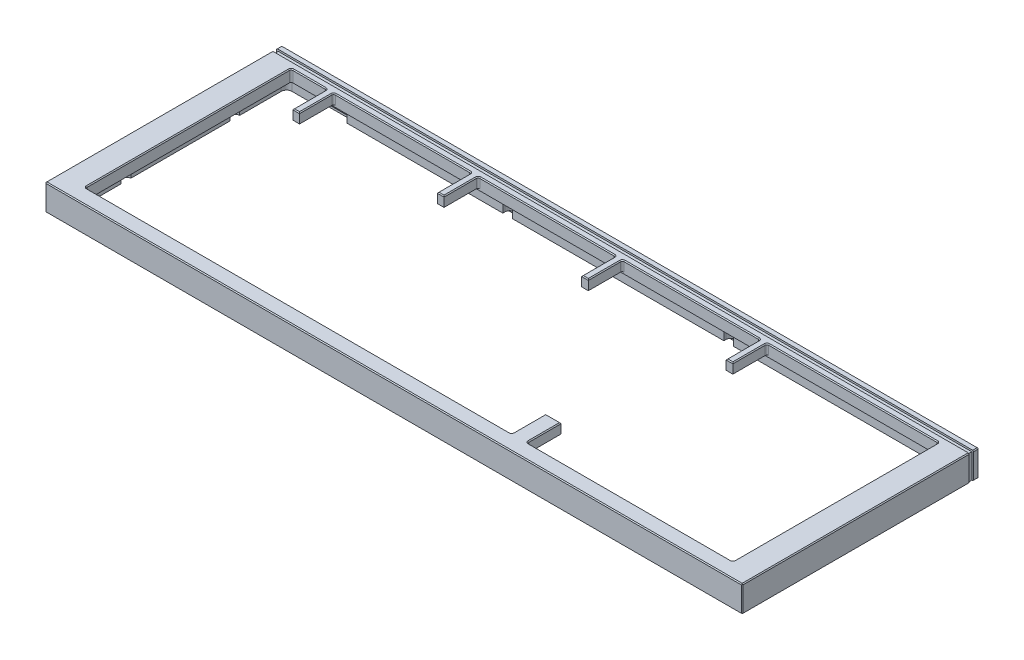
SolidWorks part; units mm, degrees
material "6061-T6 (SS)"
ref_plane "Front Plane" through (0, 0, 0) normal (0, 0, 1) x (1, 0, 0)
ref_plane "Top Plane" through (0, 0, 0) normal (0, 1, 0) x (1, 0, 0)
ref_plane "Right Plane" through (0, 0, 0) normal (1, 0, 0) x (0, 0, -1)
sketch "Sketch1" plane through (0, 0, 0) normal (0, 1, 0) x (1, 0, 0)
  line L1 (0, 0) -> (390.74, 0)
  line L2 (0, 0) -> (0, 132.7)
  line L3 (0, 132.7) -> (390.74, 132.7)
  line L4 (390.74, 0) -> (390.74, 132.7)
  line L5 (13.92, 124) -> (376.82, 124)
  line L6 (13.92, 124) -> (13.92, 8.7)
  line L7 (13.92, 8.7) -> (376.82, 8.7)
  line L8 (376.82, 124) -> (376.82, 8.7)
  point P9 (195.37, 124)
  point P10 (195.37, 132.7)
  point P11 (13.92, 66.35)
  point P12 (0, 66.35)
  dimension "D1" = 362.9
  dimension "D2" = 115.3
  dimension "D3" = 8.7
  dimension "D4" = 13.92
extrude "Main Body" add sketch "Sketch1" along normal blind 14.8
sketch "Sketch2" plane through (0, 0, 0) normal (0, -1, 0) x (1, 0, 0)
  line L0 (390.74, -132.7) -> (0, -132.7) construction
  line L1 (388.74, -130.7) -> (2, -130.7)
  line L2 (388.74, -130.7) -> (388.74, -2)
  line L3 (388.74, -2) -> (2, -2)
  line L4 (2, -130.7) -> (2, -2)
  line L5 (390.74, 0) -> (390.74, -132.7) construction
  point P4 (195.37, -130.7)
  point P7 (195.37, -132.7)
  point P8 (388.74, -66.35)
  point P11 (390.74, -66.35)
  dimension "D1" = 2
  dimension "D2" = 2
extrude "Alignment Guide" cut sketch "Sketch2" against normal blind 2 contours L2 L1 L4 L3
sketch "Sketch3" plane through (0, 14.8, 0) normal (0, 1, 0) x (1, 0, 0)
  line L0 (13.92, 8.7) -> (376.82, 8.7) construction
  line L1 (252.82, 27.8) -> (261.52, 27.8)
  line L2 (252.82, 27.8) -> (252.82, 8.7)
  line L3 (252.82, 8.7) -> (261.52, 8.7)
  line L4 (261.52, 27.8) -> (261.52, 8.7)
  line L5 (376.82, 8.7) -> (376.82, 124) construction
  line L6 (376.82, 124) -> (13.92, 124) construction
  line L7 (33.92, 124) -> (37.72, 124)
  line L8 (33.92, 124) -> (33.92, 104.9)
  line L9 (33.92, 104.9) -> (37.72, 104.9)
  line L10 (37.72, 124) -> (37.72, 104.9)
  line L11 (13.92, 124) -> (13.92, 8.7) construction
  line L12 (114.92, 124) -> (118.72, 124)
  line L13 (114.92, 124) -> (114.92, 104.9)
  line L14 (114.92, 104.9) -> (118.72, 104.9)
  line L15 (118.72, 124) -> (118.72, 104.9)
  line L16 (195.82, 124) -> (199.62, 124)
  line L17 (195.82, 124) -> (195.82, 104.9)
  line L18 (195.82, 104.9) -> (199.62, 104.9)
  line L19 (199.62, 124) -> (199.62, 104.9)
  line L20 (276.82, 124) -> (280.62, 124)
  line L21 (276.82, 124) -> (276.82, 104.9)
  line L22 (276.82, 104.9) -> (280.62, 104.9)
  line L23 (280.62, 124) -> (280.62, 104.9)
  point P8 (257.17, 8.7)
  dimension "D1" = 115.3
  dimension "D2" = 124
  dimension "D3" = 19.1
  dimension "D4" = 3.8
  dimension "D5" = 19.1
  dimension "D6" = 77.2
  dimension "D7" = 77.1
  dimension "D8" = 77.2
  dimension "D9" = 20
extrude "Blockers" add sketch "Sketch3" against normal blind 5.5
fillet "Fillet5" radius 1 14 edges at (280.62, 12.05, -124) (276.82, 12.05, -124) (195.82, 12.05, -124) (199.62, 12.05, -124) (118.72, 12.05, -124) (114.92, 12.05, -124) (33.92, 12.05, -124) (37.72, 12.05, -124) (13.92, 8.4, -124) (13.92, 8.4, -8.7) (252.82, 12.05, -8.7) (261.52, 12.05, -8.7) (376.82, 8.4, -8.7) (376.82, 8.4, -124)
sketch "Sketch4" plane through (0, 2, 0) normal (0, -1, 0) x (1, 0, 0)
  line L0 (0, 0) -> (390.74, 0) construction
  line L1 (381.27, -125.9) -> (9.47, -125.9)
  line L2 (381.27, -125.9) -> (381.27, -6.8)
  line L3 (381.27, -6.8) -> (9.47, -6.8)
  line L4 (9.47, -125.9) -> (9.47, -6.8)
  line L5 (390.74, 0) -> (390.74, -132.7) construction
  point P4 (195.37, -6.8)
  point P7 (195.37, 0)
  point P8 (381.27, -66.35)
  point P11 (390.74, -66.35)
  dimension "D1" = 119.1
  dimension "D2" = 371.8
extrude "PCB Cutout" cut sketch "Sketch4" against normal offset from surface (6.3 mm away) 6.5 up to face at (195.37, 14.8, -66.35)
fillet "Fillet4" radius 3 8 edges at (9.47, 5.15, -6.8) (9.47, 5.15, -125.9) (381.27, 5.15, -125.9) (381.27, 5.15, -6.8) (2, 1, -130.7) (2, 1, -2) (388.74, 1, -2) (388.74, 1, -130.7)
sketch "Sketch6" plane through (0, 2, 0) normal (0, -1, 0) x (1, 0, 0)
  line L0 (381.27, -9.8) -> (381.27, -122.9) construction
  line L1 (254.59, -127.1) -> (260.09, -127.1)
  line L2 (254.59, -127.1) -> (254.59, -125.9)
  line L3 (254.59, -125.9) -> (260.09, -125.9)
  line L4 (260.09, -127.1) -> (260.09, -125.9)
  line L5 (12.47, -125.9) -> (378.27, -125.9) construction
  line L11 (378.27, -6.8) -> (12.47, -6.8) construction
  line L16 (260.09, -6.8) -> (254.59, -6.8)
  line L17 (260.09, -6.8) -> (260.09, -4.8)
  line L18 (260.09, -4.8) -> (254.59, -4.8)
  line L19 (254.59, -6.8) -> (254.59, -4.8)
  line L21 (0, 0) -> (390.74, 0) construction
  line L24 (390.74, -66.35) -> (195.37, -66.35) construction
  line L25 (390.74, 0) -> (390.74, -132.7) construction
  line L26 (328.6755, -66.35) -> (328.6755, -130.7) construction
  line L27 (385.74, -130.7) -> (5, -130.7) construction
  line L28 (328.6755, -66.35) -> (328.6755, -8.7) construction
  line L29 (375.82, -8.7) -> (14.92, -8.7) construction
  line L55 (390.74, -132.7) -> (0, -132.7) construction
  line L56 (195.37, -132.7) -> (195.37, 0) construction
  line L57 (136.15, -6.8) -> (136.15, -4.8)
  line L58 (130.65, -4.8) -> (136.15, -4.8)
  line L59 (130.65, -6.8) -> (130.65, -4.8)
  line L60 (130.65, -6.8) -> (136.15, -6.8)
  line L61 (130.65, -127.1) -> (130.65, -125.9)
  line L62 (136.15, -125.9) -> (130.65, -125.9)
  line L63 (136.15, -127.1) -> (136.15, -125.9)
  line L64 (136.15, -127.1) -> (130.65, -127.1)
  circle A0 centre (381.07, -96.85) radius 2.75
  circle A1 centre (381.07, -35.85) radius 2.75
  circle A2 centre (257.34, -4.8) radius 2.75
  circle A3 centre (257.34, -127.1) radius 2.75
  circle A8 centre (133.4, -4.8) radius 2.75
  circle A9 centre (9.67, -35.85) radius 2.75
  circle A10 centre (9.67, -96.85) radius 2.75
  circle A11 centre (133.4, -127.1) radius 2.75
  point P25 (195.37, -66.35)
  point P32 (257.34, -125.9)
  point P33 (257.34, -6.8)
  line M17 (12.47, -6.8) -> (378.27, -6.8)
  line M18 (381.27, -9.8) -> (381.27, -122.9)
  line M19 (378.27, -125.9) -> (12.47, -125.9)
  line M20 (9.47, -122.9) -> (9.47, -9.8)
  dimension "D4" = 5.5
  dimension "D5" = 133.4
  dimension "D1" = 30.5
  dimension "D2" = 4.8
  dimension "D3" = 30.5
  dimension "D6" = 0.2
  dimension "D7" = 5.6
extrude "PlateTabs" cut sketch "Sketch6" against normal up to surface (6.3 mm away) contours A0 M18 | A1 M18 | A2 L19 M17 | L16 A2 L18 | A2 L17 M17 | L18 A2 | L1 A3 | L1 A3 L3 | A3 L2 M19 | A11 L64 | A11 L64 L62 | A10 M20 | A9 M20 | A8 L58 | A8 L60 L58 | A3 L4 M19 | A8 L59 M17 | L57 A8 M17 | A11 L63 M19 | L61 A11 M19 | A11 | L59 L58 L57 L60 | A3 region at (257.34, 2, -126.5102) region at (136.0681, 2, -126.1969) region at (257.34, 2, -128.2671) region at (254.6719, 2, -126.1969) region at (260.0081, 2, -126.1969) region at (133.4, 2, -126.5102) region at (133.4, 2, -128.2671) region at (130.7319, 2, -126.1969) region at (135.9001, 2, -6.317) region at (259.8401, 2, -6.317) region at (257.34, 2, -5.7445) region at (257.34, 2, -3.6329) region at (254.8399, 2, -6.317) region at (133.4, 2, -5.7445) region at (133.4, 2, -3.6329) region at (130.8999, 2, -6.317) region at (382.3459, 2, -96.85) region at (382.3459, 2, -35.85) region at (8.3941, 2, -96.85) region at (8.3941, 2, -35.85) up to face at (195.37, 8.3, -66.35)
sketch "Sketch9" plane through (0, 0, -132.7) normal (0, 0, -1) x (-1, 0, 0)
  line L1 (-40.9, 3) -> (-30.9, 3)
  line L2 (-40.9, 3) -> (-40.9, 6.8)
  line L3 (-40.9, 6.8) -> (-30.9, 6.8)
  line L4 (-30.9, 3) -> (-30.9, 6.8)
  line L7 (0, 14.8) -> (0, 0) construction
  line L8 (-390.74, 0) -> (0, 0) construction
  point P4 (-30.9, 4.9)
  point P6 (-35.9, 6.8)
  dimension "D1" = 4.9
  dimension "D2" = 3.8
  dimension "D3" = 10
  dimension "D4" = 35.9
extrude "USB Cutout" cut sketch "Sketch9" against normal up to surface (8.7 mm away) up to face at (164.89, 11.95, -124)
sketch "Sketch10" plane through (0, 0, -132.7) normal (0, 0, -1) x (-1, 0, 0)
  line L0 (-30.9, 6.8) -> (-40.9, 6.8) construction
  line L1 (-42.9, 8.8) -> (-28.9, 8.8)
  line L2 (-42.9, 8.8) -> (-42.9, 1)
  line L3 (-42.9, 1) -> (-28.9, 1)
  line L4 (-28.9, 8.8) -> (-28.9, 1)
  line L5 (-40.9, 6.8) -> (-40.9, 3) construction
  point P4 (-35.9, 8.8)
  point P7 (-35.9, 6.8)
  point P10 (-40.9, 4.9)
  point P11 (-42.9, 4.9)
  dimension "D1" = 2
  dimension "D2" = 2
extrude "USB Outline" cut sketch "Sketch10" against normal blind 1
sketch "Sketch11" plane through (0, 0, -125.9) normal (0, 0, 1) x (1, 0, 0)
  line L1 (43.4, 2) -> (28.4, 2)
  line L2 (43.4, 2) -> (43.4, 6.8)
  line L3 (43.4, 6.8) -> (28.4, 6.8)
  line L4 (28.4, 2) -> (28.4, 6.8)
  line L5 (30.9, 6.8) -> (40.9, 6.8) construction
  line L6 (40.9, 3) -> (30.9, 3) construction
  line L7 (12.47, 2) -> (130.65, 2) construction
  point P8 (35.9, 2)
  point P11 (35.9, 3)
  dimension "D1" = 15
extrude "PCB Clearance" cut sketch "Sketch11" against normal blind 3.9
fillet "Fillet6" radius 1.5 8 edges at (40.9, 6.8, -130.75) (30.9, 6.8, -130.75) (40.9, 3, -130.75) (42.9, 1, -132.2) (42.9, 8.8, -132.2) (28.9, 8.8, -132.2) (30.9, 3, -130.75) (28.9, 1, -132.2)
fillet "Fillet7" radius 2.5 2 edges at (28.4, 4.4, -129.8) (43.4, 4.4, -129.8)
sketch "Sketch12" plane through (0, 8.3, 0) normal (0, -1, 0) x (1, 0, 0)
  line L0 (195.37, -132.7) -> (195.37, 0) construction
  line L1 (390.74, -132.7) -> (0, -132.7) construction
  line L2 (14.92, -124) -> (375.82, -124) construction
  line L3 (0, 0) -> (390.74, 0) construction
  line L4 (390.74, 0) -> (390.74, -132.7) construction
  line L8 (376.82, -123) -> (376.82, -9.7) construction
  line L9 (375.82, -8.7) -> (14.92, -8.7) construction
  arc A0 (381.27, -38.5927) -> (381.27, -33.1073) centre (381.07, -35.85) ccw construction
  arc A1 (381.27, -99.5927) -> (381.27, -94.1073) centre (381.07, -96.85) ccw construction
  point P0 (257.34, -127.1)
  point P1 (381.42, -96.85)
  point P2 (381.42, -35.85)
  point P3 (257.34, -4.8)
  point P8 (133.4, -4.8)
  point P10 (9.32, -35.85)
  point P14 (9.32, -96.85)
  point P16 (133.4, -127.1)
  point P34 (383.82, -35.85)
  point P39 (383.82, -96.85)
  dimension "D1" = 3.1
  dimension "D2" = 3.9
  dimension "D3" = 4.6
  dimension "D4" = 133.4
sketch "Sketch14" plane through (0, 2, 0) normal (0, -1, 0) x (1, 0, 0)
  line L0 (195.37, -132.7) -> (195.37, 0) construction
  line L1 (390.74, -132.7) -> (0, -132.7) construction
  line L2 (0, 0) -> (390.74, 0) construction
  line L5 (195.37, -66.35) -> (390.74, -66.35) construction
  line L6 (390.74, 0) -> (390.74, -132.7) construction
  line L7 (388.74, -127.7) -> (388.74, -5) construction
  line L8 (385.74, -130.7) -> (5, -130.7) construction
  line L9 (385.74, -2) -> (5, -2) construction
  point P8 (385.04, -111.35)
  point P9 (385.04, -66.35)
  point P10 (385.04, -21.35)
  point P11 (280.74, -4.4)
  point P20 (280.74, -128.3)
  point P22 (110, -4.4)
  point P28 (110, -128.3)
  point P29 (5.7, -21.35)
  point P30 (5.7, -66.35)
  point P31 (5.7, -111.35)
  dimension "D1" = 2.4
  dimension "D2" = 2.4
  dimension "D3" = 110
  dimension "D4" = 45
  dimension "D5" = 45
  dimension "D6" = 3.7
chamfer "Chamfer1" distance 0.5 42 edges at (14.2129, 14.8, -8.9929) (133.37, 14.8, -8.7) (252.5271, 14.8, -8.9929) (252.82, 14.8, -18.75) (257.17, 14.8, -27.8) (261.52, 14.8, -18.75) (261.8129, 14.8, -8.9929) (319.17, 14.8, -8.7) (376.5271, 14.8, -8.9929) (376.82, 14.8, -66.35) (376.5271, 14.8, -123.7071) (328.72, 14.8, -124) (280.9129, 14.8, -123.7071) (280.62, 14.8, -113.95) (278.72, 14.8, -104.9) (276.82, 14.8, -113.95) (276.5271, 14.8, -123.7071) (238.22, 14.8, -124) (199.9129, 14.8, -123.7071) (199.62, 14.8, -113.95) (197.72, 14.8, -104.9) (195.82, 14.8, -113.95) (195.5271, 14.8, -123.7071) (157.27, 14.8, -124) (119.0129, 14.8, -123.7071) (118.72, 14.8, -113.95) (116.82, 14.8, -104.9) (114.92, 14.8, -113.95) (114.6271, 14.8, -123.7071) (76.32, 14.8, -124) (38.0129, 14.8, -123.7071) (37.72, 14.8, -113.95) (35.82, 14.8, -104.9) (33.92, 14.8, -113.95) (33.6271, 14.8, -123.7071) (23.92, 14.8, -124) (14.2129, 14.8, -123.7071) (13.92, 14.8, -66.35) (195.37, 14.8, -132.7) (390.74, 14.8, -66.35) (195.37, 14.8, 0) (0, 14.8, -66.35)
chamfer "Chamfer2" distance 0.5 8 edges at (0, 7.15, -132.7) (195.37, 0, -132.7) (390.74, 7.15, -132.7) (390.74, 0, -66.35) (390.74, 7.15, 0) (0, 7.15, 0) (195.37, 0, 0) (0, 0, -66.35)
sketch "Sketch27" plane through (0, 14.8, 0) normal (0, 1, 0) x (1, 0, 0)
  line L0 (0, 0.5) -> (0, 132.2) construction
  line L1 (0, 129.7) -> (390.74, 129.7)
  line L2 (0, 129.7) -> (0, 127.2)
  line L3 (0, 127.2) -> (390.74, 127.2)
  line L4 (390.74, 129.7) -> (390.74, 127.2)
  line L5 (390.74, 132.2) -> (390.74, 0.5) construction
  line L8 (0.5, 132.7) -> (390.24, 132.7) construction
  dimension "D1" = 2.5
  dimension "D2" = 3
extrude "Cut-Extrude11" cut sketch "Sketch27" against normal blind 1
sketch "Sketch28" plane through (0, 13.8, 0) normal (0, 1, 0) x (1, 0, 0)
  line L1 (0, 129.7) -> (1, 129.7)
  line L2 (0, 129.7) -> (0, 127.2)
  line L3 (0, 127.2) -> (1, 127.2)
  line L4 (1, 129.7) -> (1, 127.2)
  line L5 (389.74, 129.7) -> (390.74, 129.7)
  line L6 (389.74, 129.7) -> (389.74, 127.2)
  line L7 (389.74, 127.2) -> (390.74, 127.2)
  line L8 (390.74, 129.7) -> (390.74, 127.2)
  line L9 (390.74, 129.7) -> (0, 129.7) construction
  line L10 (0, 127.2) -> (390.74, 127.2) construction
  dimension "D1" = 1
  dimension "D2" = 1
extrude "Cut-Extrude12" cut sketch "Sketch28" against normal through all
sketch "Sketch21" [suppressed] plane through (0, 14.8, 0) normal (0, 1, 0) x (1, 0, 0)
  line L0 (0.5, 132.7) -> (390.24, 132.7) construction
  line L1 (382.53, 132.7) -> (385.03, 132.7)
  line L2 (382.53, 132.7) -> (382.53, 72.7)
  line L3 (382.53, 72.7) -> (385.03, 72.7)
  line L4 (385.03, 132.7) -> (385.03, 72.7)
  line L5 (390.74, 132.2) -> (390.74, 129.7) construction
  line L6 (390.74, 129.1) -> (294.74, 129.1)
  line L7 (390.74, 129.1) -> (390.74, 127.6)
  line L8 (390.74, 127.6) -> (294.74, 127.6)
  line L9 (294.74, 129.1) -> (294.74, 127.6)
  line L10 (362.9081, 132.2) -> (362.9081, 124.5) construction
  line L11 (390.24, 132.2) -> (0.5, 132.2) construction
  line L12 (281.62, 124.5) -> (375.82, 124.5) construction
  line L13 (365.5702, 129.1) -> (365.5702, 127.6) construction
  line L14 (377.32, 119.5259) -> (390.24, 119.5259) construction
  line L15 (377.32, 123) -> (377.32, 9.7) construction
  line L16 (390.24, 0.5) -> (390.24, 127.2) construction
  line L17 (382.53, 116.0504) -> (385.03, 116.0504) construction
  point P28 (383.78, 116.0504)
  point P29 (383.78, 119.5259)
  point P30 (365.5702, 128.35)
  point P31 (362.9081, 128.35)
  dimension "D1" = 2.5
  dimension "D2" = 1.5
  dimension "D3" = 60
  dimension "D4" = 96
extrude "Cut-Extrude5" [suppressed] cut sketch "Sketch21" against normal blind 1 contours L4 L3 L2 L1 | L8 L9 L6 L7
sketch "Sketch23" [suppressed] plane through (390.74, 0, 0) normal (1, 0, 0) x (0, 0, -1)
  line L0 (129.1, 13.8) -> (129.1, 14.3) construction
  line L1 (127.6, 13.8) -> (129.1, 13.8)
  line L2 (127.6, 13.8) -> (127.6, 0)
  line L3 (127.6, 0) -> (129.1, 0)
  line L4 (129.1, 13.8) -> (129.1, 0)
extrude "Cut-Extrude6" [suppressed] cut sketch "Sketch23" against normal blind 1
sketch "Sketch20" plane through (0, 14.8, 0) normal (0, 1, 0) x (1, 0, 0)
  line L0 (0, 0.5) -> (0, 127.2) construction
  line L1 (0, 129.1) -> (390.74, 129.1)
  line L2 (0, 129.1) -> (0, 127.6)
  line L3 (0, 127.6) -> (390.74, 127.6)
  line L4 (390.74, 129.1) -> (390.74, 127.6)
  line L5 (390.74, 132.2) -> (390.74, 129.7) construction
  line L6 (0.5, 132.7) -> (390.24, 132.7) construction
  line L7 (381.7523, 132.7) -> (384.2523, 132.7)
  line L8 (381.7523, 132.7) -> (381.7523, 0)
  line L9 (381.7523, 0) -> (384.2523, 0)
  line L10 (384.2523, 132.7) -> (384.2523, 0)
  line L11 (390.24, 0) -> (0.5, 0) construction
  line L12 (376.82, 111.1489) -> (390.74, 111.1489) construction
  line L13 (376.82, 9.7) -> (376.82, 123) construction
  line L14 (381.7523, 114.604) -> (384.2523, 114.604) construction
  line L15 (369.2566, 124.5) -> (369.2566, 132.2) construction
  line L16 (281.62, 124.5) -> (375.82, 124.5) construction
  line L17 (390.24, 132.2) -> (0.5, 132.2) construction
  line L18 (371.0168, 127.6) -> (371.0168, 129.1) construction
  point P30 (371.0168, 128.35)
  point P31 (369.2566, 128.35)
  dimension "D1" = 2.5
  dimension "D2" = 1.5
extrude "Cut-Extrude4" [suppressed] cut sketch "Sketch20" against normal blind 1
sketch "Sketch19" plane through (0, 14.8, 0) normal (0, 1, 0) x (1, 0, 0)
  line L0 (0.5, 132.7) -> (390.24, 132.7) construction
  line L1 (5.46, 132.7) -> (8.46, 132.7)
  line L2 (5.46, 132.7) -> (5.46, 0)
  line L3 (5.46, 0) -> (8.46, 0)
  line L4 (8.46, 132.7) -> (8.46, 0)
  line L7 (382.28, 132.7) -> (385.28, 132.7)
  line L8 (382.28, 132.7) -> (382.28, 0)
  line L9 (382.28, 0) -> (385.28, 0)
  line L10 (385.28, 132.7) -> (385.28, 0)
  line L11 (390.24, 0) -> (0.5, 0) construction
  line L12 (377.32, 110.209) -> (390.24, 110.209) construction
  line L13 (377.32, 123) -> (377.32, 9.7) construction
  line L14 (390.24, 0.5) -> (390.24, 127.2) construction
  line L15 (382.28, 106.8719) -> (385.28, 106.8719) construction
  line L16 (0.5, 106.8719) -> (13.42, 106.8719) construction
  line L17 (0.5, 132.2) -> (0.5, 129.7) construction
  line L18 (13.42, 9.7) -> (13.42, 123) construction
  line L19 (5.46, 102.7297) -> (8.46, 102.7297) construction
  point P12 (383.78, 106.8719)
  point P14 (383.78, 110.209)
  point P30 (6.96, 102.7297)
  point P31 (6.96, 106.8719)
  dimension "D1" = 3
  dimension "D2" = 3
extrude "Cut-Extrude3" [suppressed] cut sketch "Sketch19" against normal blind 1
sketch "Sketch17" plane through (0, 14.8, 0) normal (0, 1, 0) x (1, 0, 0)
  line L0 (390.24, 0.5) -> (390.24, 127.2) construction
  line L1 (5.71, 129.6) -> (385.03, 129.6)
  line L2 (5.71, 129.6) -> (5.71, -1.9)
  line L3 (5.71, -1.9) -> (385.03, -1.9)
  line L4 (385.03, 129.6) -> (385.03, -1.9)
  line L5 (8.21, 127.1) -> (382.53, 127.1)
  line L6 (8.21, 127.1) -> (8.21, 0.6)
  line L7 (8.21, 0.6) -> (382.53, 0.6)
  line L8 (382.53, 127.1) -> (382.53, 0.6)
  line L9 (390.24, 132.2) -> (0.5, 132.2) construction
  line L10 (21.2533, 132.2) -> (21.2533, 124.5) construction
  line L11 (14.92, 124.5) -> (32.92, 124.5) construction
  line L12 (25.2757, 129.6) -> (25.2757, 127.1) construction
  line L13 (0.5, 116.1326) -> (13.42, 116.1326) construction
  line L14 (0.5, 132.2) -> (0.5, 129.7) construction
  line L15 (13.42, 9.7) -> (13.42, 123) construction
  line L16 (5.71, 120.1548) -> (8.21, 120.1548) construction
  point P8 (382.53, 63.85)
  point P9 (385.03, 63.85)
  point P12 (390.24, 63.85)
  point P13 (195.37, 129.6)
  point P14 (195.37, 127.1)
  point P17 (195.37, 132.2)
  point P24 (25.2757, 128.35)
  point P25 (21.2533, 128.35)
  point P34 (6.96, 116.1326)
  point P35 (6.96, 120.1548)
  dimension "D1" = 2.5
  dimension "D2" = 2.5
extrude "Cut-Extrude1" [suppressed] cut sketch "Sketch17" against normal blind 1
hole_wizard "M3x0.5 Tapped Hole1" positions "3DSketch1" profile "Sketch29" tap size "M3x0.5" standard "ANSI Metric"
sketch3d "3DSketch1"
  point P0 (385.04, 2, -111.35)
  point P3 (385.04, 2, -21.35)
  point P6 (280.74, 2, -4.4)
  point P9 (110, 2, -4.4)
  point P12 (5.7, 2, -21.35)
  point P15 (5.7, 2, -66.35)
  point P18 (5.7, 2, -111.35)
  point P21 (110, 2, -128.3)
  point P24 (280.74, 2, -128.3)
  point P28 (385.04, 2, -66.35)
sketch "Sketch29" plane through (385.04, 2, -111.35) normal (1, 0, 0) x (0, 0, -1)
  line L0 (0, 0) -> (0, 4.7511)
  line L1 (0, 4.7511) -> (1.25, 4)
  line L2 (1.25, 4) -> (1.25, 0)
  line L5 (1.25, 0) -> (0, 0)
  line L10 (0, 4.7511) -> (-1.25, 4) construction
  line L11 (0, -6.35) -> (0, 107.95) construction
  dimension "Tap Drill Dia." = 2.5
  dimension "Tap Drill Depth" = 4
  dimension "Drill Angle" = 118
cosmetic thread "Hole Thread1" parameters "D1"=4, "D2"=3
cosmetic thread "Hole Thread2" parameters "D1"=4, "D2"=3
cosmetic thread "Hole Thread3" parameters "D1"=4, "D2"=3
cosmetic thread "Hole Thread4" parameters "D1"=4, "D2"=3
cosmetic thread "Hole Thread5" parameters "D1"=4, "D2"=3
cosmetic thread "Hole Thread6" parameters "D1"=4, "D2"=3
cosmetic thread "Hole Thread7" parameters "D1"=4, "D2"=3
cosmetic thread "Hole Thread8" parameters "D1"=4, "D2"=3
cosmetic thread "Hole Thread9" parameters "D1"=4, "D2"=3
cosmetic thread "Hole Thread18" parameters "D1"=4, "D2"=3
hole_wizard "M2x0.4 Tapped Hole4" positions "3DSketch3" profile "Sketch31" tap size "M2x0.4" standard "ANSI Metric"
sketch3d "3DSketch3"
  line L0 (381.07, 8.3, -96.85) -> (381.07, 2, -96.85) construction
  line L1 (381.07, 8.3, -35.85) -> (381.07, 2, -35.85) construction
  line L2 (9.67, 8.3, -35.85) -> (9.67, 2, -35.85) construction
  line L3 (9.67, 8.3, -96.85) -> (9.67, 2, -96.85) construction
  point P0 (381.07, 8.3, -96.85)
  point P5 (381.07, 8.3, -35.85)
  point P9 (257.34, 8.3, -4.8)
  point P12 (133.4, 8.3, -4.8)
  point P15 (9.67, 8.3, -35.85)
  point P19 (9.67, 8.3, -96.85)
  point P23 (133.4, 8.3, -127.1)
  point P26 (257.34, 8.3, -127.1)
sketch "Sketch31" plane through (381.07, 8.3, -96.85) normal (1, 0, 0) x (0, 0, -1)
  line L0 (0, 0) -> (0, 4.4807)
  line L1 (0, 4.4807) -> (0.8, 4)
  line L2 (0.8, 4) -> (0.8, 0)
  line L5 (0.8, 0) -> (0, 0)
  line L10 (0, 4.4807) -> (-0.8, 4) construction
  line L11 (0, -6.35) -> (0, 107.95) construction
  dimension "Tap Drill Dia." = 1.6
  dimension "Tap Drill Depth" = 4
  dimension "Drill Angle" = 118
cosmetic thread "Hole Thread19" parameters "D1"=4, "D2"=2
cosmetic thread "Hole Thread20" parameters "D1"=4, "D2"=2
cosmetic thread "Hole Thread21" parameters "D1"=4, "D2"=2
cosmetic thread "Hole Thread22" parameters "D1"=4, "D2"=2
cosmetic thread "Hole Thread23" parameters "D1"=4, "D2"=2
cosmetic thread "Hole Thread24" parameters "D1"=4, "D2"=2
cosmetic thread "Hole Thread25" parameters "D1"=4, "D2"=2
cosmetic thread "Hole Thread26" parameters "D1"=4, "D2"=2
